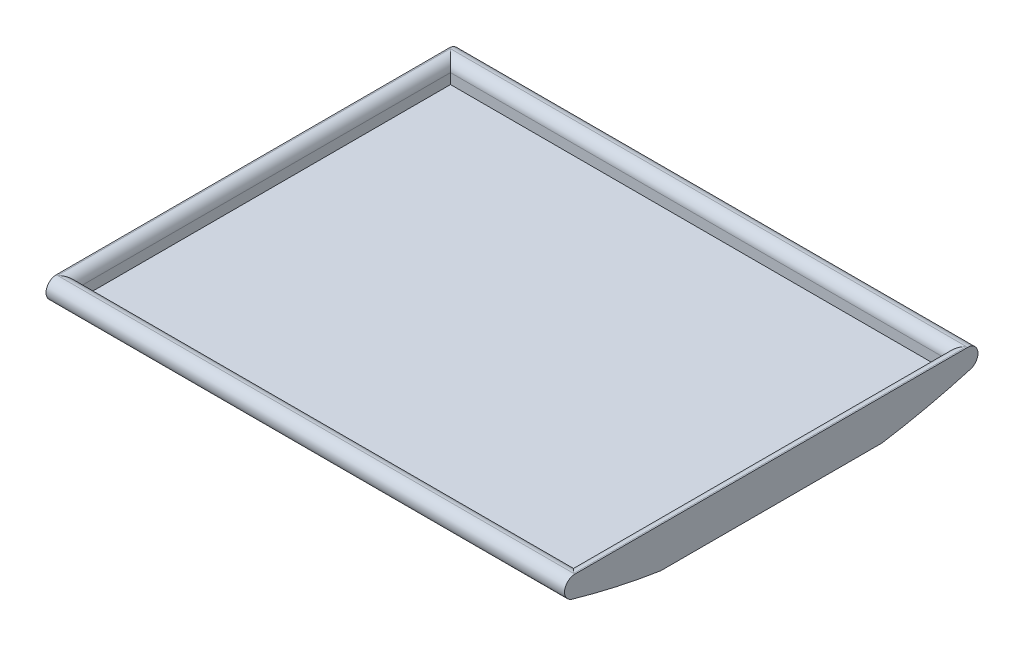
SolidWorks part; units mm, degrees
ref_plane "前视基准面" through (0, 0, 0) normal (0, 0, 1) x (1, 0, 0)
ref_plane "上视基准面" through (0, 0, 0) normal (0, 1, 0) x (1, 0, 0)
ref_plane "右视基准面" through (0, 0, 0) normal (1, 0, 0) x (0, 0, -1)
sketch "草图1" plane through (0, 0, 0) normal (1, 0, 0) x (0, 0, -1)
  line L0 (6.066, 0) -> (43.934, 0)
  line L1 (35.6603, -3.8615) -> (14.3397, -3.8615)
  arc A0 (5.7875, -1.9604) -> (14.3397, -3.8615) centre (25, 64.2811) ccw
  arc A1 (5.7875, -1.9604) -> (6.066, 0) centre (6.066, -1) cw
  arc A2 (43.934, 0) -> (44.2125, -1.9604) centre (43.934, -1) cw
  arc A3 (35.6603, -3.8615) -> (44.2125, -1.9604) centre (25, 64.2811) ccw
  point P6 (0, 0)
extrude "凸台-拉伸1" add sketch "草图1" along normal blind 50
sketch "草图2" plane through (0, 0, 0) normal (0, 1, 0) x (1, 0, 0)
  line L1 (1.124, 42.9447) -> (48.876, 42.9447)
  line L2 (1.124, 42.9447) -> (1.124, 7.0553)
  line L3 (1.124, 7.0553) -> (48.876, 7.0553)
  line L4 (48.876, 42.9447) -> (48.876, 7.0553)
extrude "切除-拉伸1" cut sketch "草图2" against normal blind 2
fillet "圆角1" radius 1 4 edges at (25, 0, -7.0553) (48.876, 0, -25) (25, 0, -42.9447) (1.124, 0, -25)
scale "缩放比例1" scale about centroid uniform scaling yes scale factor 0.4
